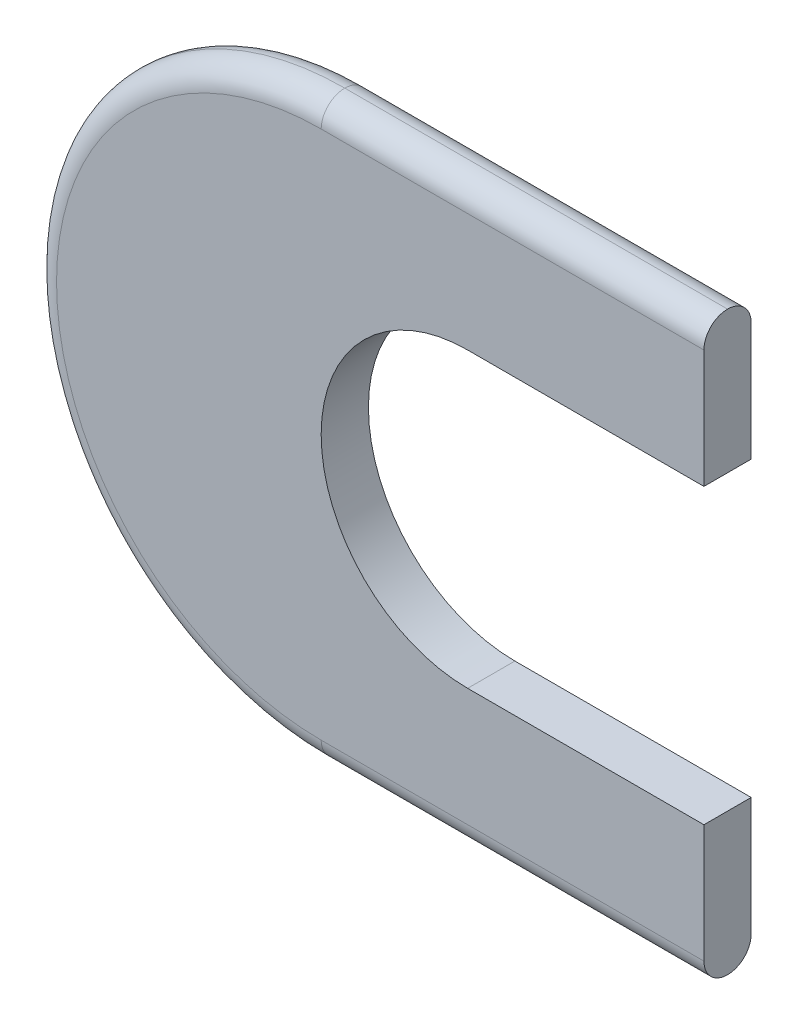
SolidWorks part; units mm, degrees
ref_plane "Front Plane" through (0, 0, 0) normal (0, 0, 1) x (1, 0, 0)
ref_plane "Top Plane" through (0, 0, 0) normal (0, 1, 0) x (1, 0, 0)
ref_plane "Right Plane" through (0, 0, 0) normal (1, 0, 0) x (0, 0, -1)
sketch "Sketch1" plane through (0, 0, 0) normal (0, 0, 1) x (1, 0, 0)
  line L0 (0, 3.1) -> (5, 3.1)
  line L1 (5, 3.1) -> (5, 6.1)
  line L2 (5, 6.1) -> (-3.1, 6.1)
  line L3 (0, 0) -> (6.176, 0) construction
  line L4 (0, -3.1) -> (5, -3.1)
  line L5 (5, -3.1) -> (5, -6.1)
  line L6 (5, -6.1) -> (-3.1, -6.1)
  circle A0 centre (0, 0) radius 3.1 construction
  arc A1 (0, 3.1) -> (0, -3.1) centre (0, 0) ccw
  arc A2 (-3.1, 6.1) -> (-3.1, -6.1) centre (-3.1, 0) ccw
extrude "Boss-Extrude1" add sketch "Sketch1" along normal blind 1
fillet "Fillet1" radius 0.5 6 edges at (0.95, 6.1, 0) (0.95, -6.1, 0) (0.95, 6.1, 1) (0.95, -6.1, 1) (-9.2, 0, 0) (-9.2, 0, 1)
